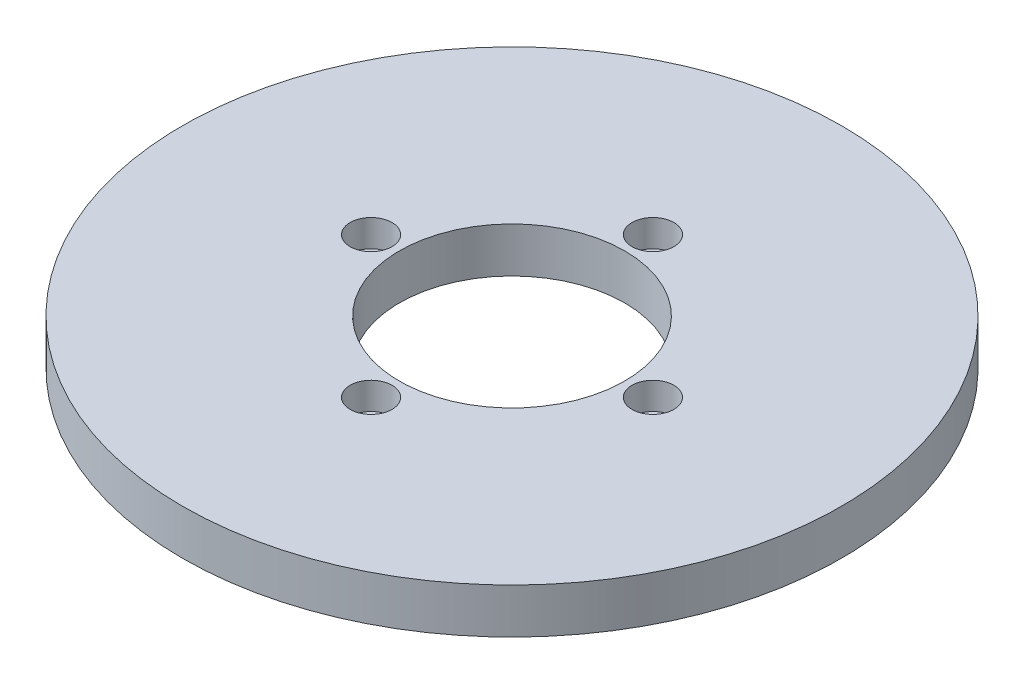
SolidWorks part; units mm, degrees
ref_plane "Front Plane" through (0, 0, 0) normal (0, 0, 1) x (1, 0, 0)
ref_plane "Top Plane" through (0, 0, 0) normal (0, 1, 0) x (1, 0, 0)
ref_plane "Right Plane" through (0, 0, 0) normal (1, 0, 0) x (0, 0, -1)
sketch "Sketch1" plane through (0, 0, 0) normal (0, 1, 0) x (1, 0, 0)
  circle A0 centre (0, 0) radius 95
  dimension "FLANGE_OD" = 190
extrude "Boss-Extrude1" add sketch "Sketch1" along normal blind 13
sketch "Sketch2" plane through (0, 0, 0) normal (0, 1, 0) x (1, 0, 0)
  circle A0 centre (0, 0) radius 32.5
  dimension "BORE_D" = 65
extrude "Cut-Extrude1" cut sketch "Sketch2" along normal through all
sketch "Sketch3" plane through (0, 13, 0) normal (0, 1, 0) x (1, 0, 0)
  circle A0 centre (0, 0) radius 40.6281 construction
  circle A1 centre (-40.6281, 0) radius 6.0383
  dimension "BOLT_D" = 12.0765
  dimension "BOLT_PCD" = 81.2561
extrude "Cut-Extrude2" cut sketch "Sketch3" against normal blind 7.8151
pattern_circular "CirPattern1" count 4 over 360 about axis through (0, 0, 0) along (0, 1, 0) of "Cut-Extrude2"
